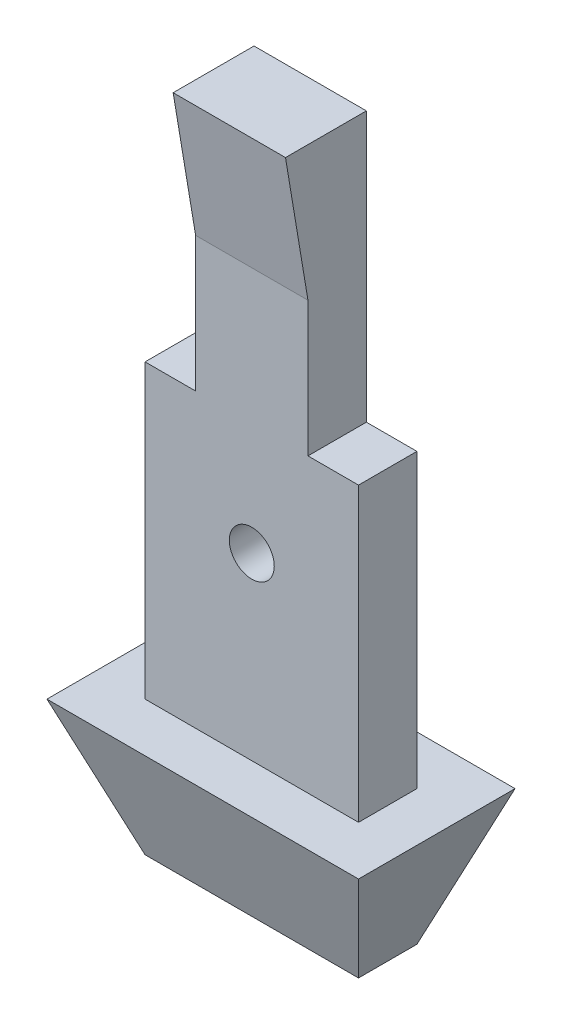
SolidWorks part; units mm, degrees
ref_plane "Plano frontal" through (0, 0, 0) normal (0, 0, 1) x (1, 0, 0)
ref_plane "Plano superior" through (0, 0, 0) normal (0, 1, 0) x (1, 0, 0)
ref_plane "Plano direito" through (0, 0, 0) normal (1, 0, 0) x (0, 0, -1)
sketch "Esboço1" plane through (0, 0, 0) normal (0, 0, 1) x (1, 0, 0)
  line L0 (0, 0) -> (0, 61.3289) construction
  line L1 (-2.5, 31) -> (2.5, 31)
  line L2 (2.5, 31) -> (2.5, 19)
  line L3 (2.5, 19) -> (4.75, 19)
  line L4 (4.75, 19) -> (4.75, 0)
  line L5 (4.75, 0) -> (-4.75, 0)
  line L6 (-4.75, 19) -> (-4.75, 0)
  line L7 (-2.5, 19) -> (-4.75, 19)
  line L8 (-2.5, 31) -> (-2.5, 19)
  circle A0 centre (0, 14) radius 1
  point P13 (0, 31)
  dimension "D5" = 2
  dimension "D1" = 19
  dimension "D2" = 9.5
  dimension "D3" = 5
  dimension "D4" = 12
  dimension "D6" = 5
extrude "Ressalto-extrusão1" add sketch "Esboço1" along normal blind 2.6
sketch "Esboço2" plane through (0, 0, 0) normal (0, -1, 0) x (1, 0, 0)
  line L4 (-4.75, 0) -> (4.75, 0)
  line L5 (4.75, 0) -> (4.75, 2.6)
  line L6 (4.75, 2.6) -> (-4.75, 2.6)
  line L7 (-4.75, 2.6) -> (-4.75, 0)
  line L8 (-4.75, 0) -> (4.75, 0)
  line L9 (4.75, 0) -> (4.75, 2.6)
  line L10 (4.75, 2.6) -> (-4.75, 2.6)
  line L11 (-4.75, 2.6) -> (-4.75, 0)
  dimension "D1" = 0
extrude "Ressalto-extrusão2" add sketch "Esboço2" against normal blind 6 draft 20 draft outward yes
sketch "Esboço3" plane through (2.5, 0, 0) normal (1, 0, 0) x (0, 0, -1)
  line L0 (-2.6, 31) -> (-3.6, 31)
  line L1 (-3.6, 31) -> (-2.6, 25)
  line L2 (-2.6, 19) -> (-2.6, 31) construction
  line L3 (-2.6, 31) -> (-2.6, 25)
  dimension "D1" = 1
extrude "Ressalto-extrusão3" add sketch "Esboço3" against normal up to surface (5 mm away) up to face at (-2.5, 25, 1.3)
